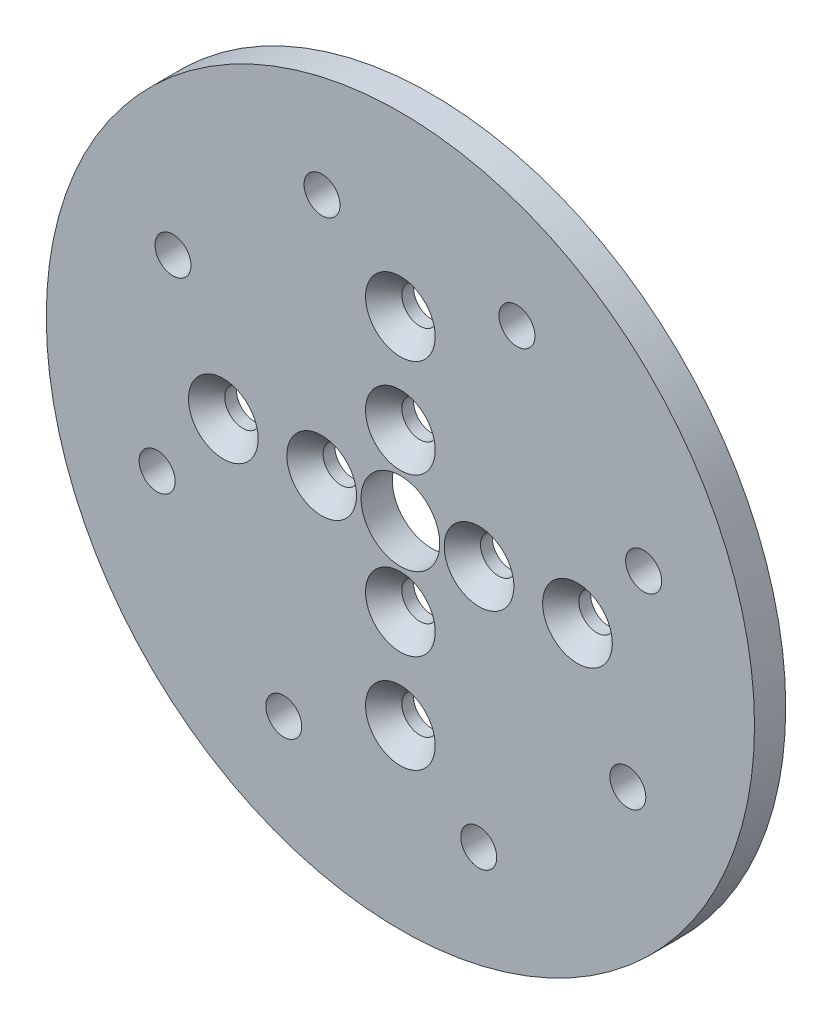
SolidWorks part; units mm, degrees
material "6061-T6 (SS)"
ref_plane "Front" through (0, 0, 0) normal (0, 0, 1) x (1, 0, 0)
ref_plane "Top" through (0, 0, 0) normal (0, 1, 0) x (1, 0, 0)
ref_plane "Right" through (0, 0, 0) normal (1, 0, 0) x (0, 0, -1)
ref_axis "side-side" through (80.9, 0, 0) along (-1, 0, 0)
ref_axis "up-down" through (0, 50, 0) along (0, -1, 0)
ref_axis "front-back" through (0, 0, -80.9) along (0, 0, 1)
sketch "Sketch2" plane through (0, 0, 0) normal (0, 0, 1) x (1, 0, 0)
  line L0 (0, 0) -> (-24.7287, -7.9658) construction
  line L1 (0, 0) -> (-7.9658, 24.7287) construction
  circle A1 centre (0, 0) radius 25.98 construction
  circle A3 centre (0, 18) radius 1.8542
  circle A4 centre (0, -18) radius 1.8542
  circle A5 centre (18, 0) radius 1.8542
  circle A12 centre (-11.8532, -23.1184) radius 2.35
  circle A13 centre (24.7287, 7.9658) radius 2.35
  circle A14 centre (11.8532, 23.1184) radius 2.35
  circle A15 centre (-7.9658, 24.7287) radius 2.35
  circle A16 centre (-23.1184, 11.8532) radius 2.35
  circle A17 centre (-24.7287, -7.9658) radius 2.35
  point P11 (23.1184, -11.8532)
  point P13 (0, 0)
  point P15 (0, 0)
  point P30 (7.9658, -24.7287)
  dimension "D1" = 45
sketch "Sketch1" plane through (0, 0, 0) normal (0, 0, 1) x (1, 0, 0)
  line L1 (-36, 100) -> (36, 100) construction
  line L2 (-36, 100) -> (-36, 0) construction
  line L3 (-36, 0) -> (36, 0) construction
  line L4 (36, 100) -> (36, 0) construction
  arc A0 (-36, 0) -> (36, 0) centre (0, 0) ccw
  circle A1 centre (0, 0) radius 4
  circle A2 centre (-8, 0) radius 1.85 construction
  circle A3 centre (0, -8) radius 1.85 construction
  circle A4 centre (0, 0) radius 8 construction
  circle A5 centre (0, 8) radius 1.85 construction
  circle A6 centre (8, 0) radius 1.85 construction
  arc A7 (-36, 0) -> (36, 0) centre (0, 0) cw
  dimension "D1" = 8
  dimension "D4" = 16
  dimension "D5" = 3.7
  dimension "D2" = 72
  dimension "D3" = 100
extrude "Boss-Extrude1" add sketch "Sketch1" along normal blind 3.175
hole_wizard "#6 Clearance Hole1" positions "Sketch3" profile "Sketch4" hole size "#6" standard "ANSI Inch"
sketch "Sketch3" plane through (0, 0, 0) normal (0, 0, 1) x (1, 0, 0)
  point P0 (-11.8532, -23.1184)
  point P3 (24.7287, 7.9658)
  point P6 (11.8532, 23.1184)
  point P9 (-7.9658, 24.7287)
  point P12 (-23.1184, 11.8532)
  point P15 (-24.7287, -7.9658)
  point P18 (7.9658, -24.7287)
  point P21 (23.1184, -11.8532)
sketch "Sketch4" plane through (-11.8532, -23.1184, 0) normal (1, 0, 0) x (0, 1, 0)
  line L0 (0, 0) -> (0, 9.0989)
  line L1 (0, 9.0989) -> (1.8288, 8)
  line L2 (1.8288, 8) -> (1.8288, 0)
  line L5 (1.8288, 0) -> (0, 0)
  line L10 (0, 9.0989) -> (-1.8288, 8) construction
  line L11 (0, -6.35) -> (0, 107.95) construction
  dimension "Hole Dia." = 3.6576
  dimension "Hole Depth" = 8
  dimension "Drill Angle" = 118
hole_wizard "CSK for #6 Flat Head Machine Screw2" positions "Sketch5" profile "Sketch6" countersink size "#6" standard "ANSI Inch"
sketch "Sketch5" plane through (0, 0, 3.175) normal (0, 0, -1) x (-1, 0, 0)
  line L0 (0, 0) -> (18, 0) construction
  line L1 (0, 0) -> (-18, 0) construction
  point P0 (0, 18)
  point P3 (-18, 0)
  point P6 (0, -18)
  point P9 (18, 0)
  point P17 (0, 8)
  point P20 (-8, 0)
  point P23 (0, -8)
  point P26 (8, 0)
sketch "Sketch6" plane through (0, 18, 3.175) normal (1, 0, 0) x (0, -1, 0)
  line L0 (0, 0) -> (0, 9.0989)
  line L1 (0, 9.0989) -> (1.8288, 8)
  line L2 (1.8288, 8) -> (1.8288, 1.9723)
  line L3 (1.8288, 1.9723) -> (3.5433, 0)
  line L5 (3.5433, 0) -> (0, 0)
  line L6 (-1.8288, 1.9723) -> (-3.5433, 0) construction
  line L10 (0, 9.0989) -> (-1.8288, 8) construction
  line L11 (0, -6.35) -> (0, 107.95) construction
  dimension "Hole Dia." = 3.6576
  dimension "Hole Depth" = 8
  dimension "Near C'Sink Dia." = 7.0866
  dimension "Near C'Sink Angle" = 82
  dimension "Drill Angle" = 118
